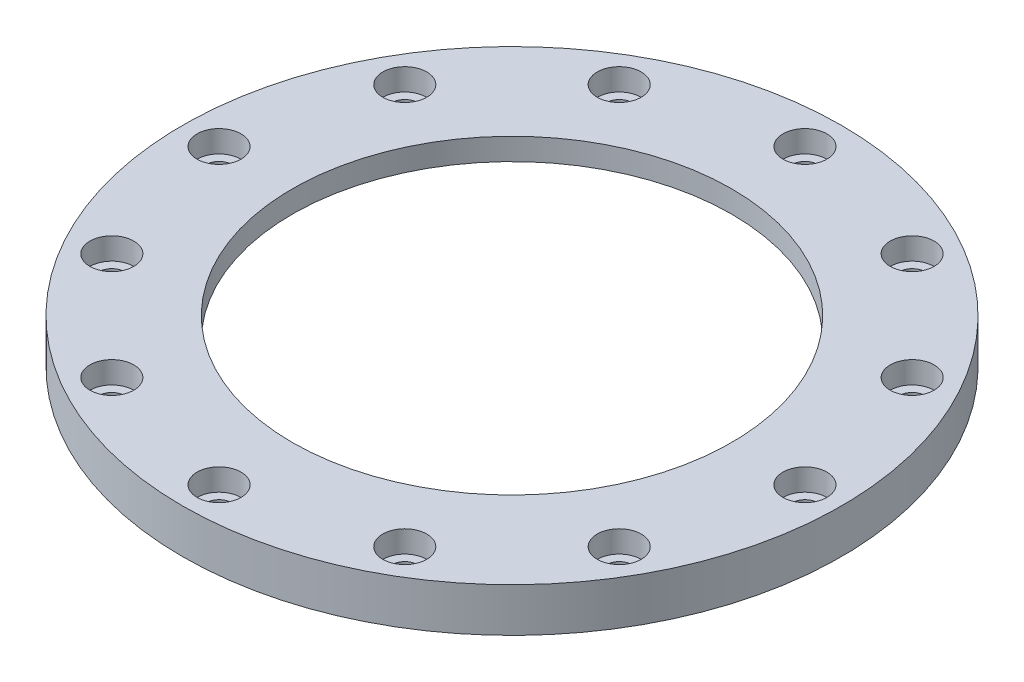
SolidWorks part; units mm, degrees
ref_plane "Front Plane" through (0, 0, 0) normal (0, 0, 1) x (1, 0, 0)
ref_plane "Top Plane" through (0, 0, 0) normal (0, 1, 0) x (1, 0, 0)
ref_plane "Right Plane" through (0, 0, 0) normal (1, 0, 0) x (0, 0, -1)
sketch "Sketch1" plane through (0, 0, 0) normal (0, 1, 0) x (1, 0, 0)
  line L0 (0, 0) -> (0, 52.0165) construction
  circle A0 centre (0, 0) radius 45
  circle A1 centre (0, 0) radius 30
  circle A2 centre (0, 0) radius 40 construction
  circle A3 centre (0, 40) radius 1.75
  circle A4 centre (0, 0) radius 36 construction
  circle A5 centre (20, 34.641) radius 1.75
  circle A6 centre (34.641, 20) radius 1.75
  circle A7 centre (40, 0) radius 1.75
  circle A8 centre (34.641, -20) radius 1.75
  circle A9 centre (20, -34.641) radius 1.75
  circle A10 centre (0, -40) radius 1.75
  circle A11 centre (-20, -34.641) radius 1.75
  circle A12 centre (-34.641, -20) radius 1.75
  circle A13 centre (-40, 0) radius 1.75
  circle A14 centre (-34.641, 20) radius 1.75
  circle A15 centre (-20, 34.641) radius 1.75
  point P21 (0, 0)
  point P34 (0, 0)
  point P48 (0, 0)
  point P72 (0, 0)
  dimension "D1" = 90
  dimension "D2" = 60
  dimension "D4" = 3.5
  dimension "D5" = 72
  dimension "D6" = 12
  dimension "D3" = 80
extrude "Boss-Extrude1" add sketch "Sketch1" along normal blind 6
sketch "Sketch2" plane through (0, 0, 0) normal (0, -1, 0) x (1, 0, 0)
  circle A0 centre (0, 0) radius 36
  dimension "D1" = 72
extrude "Cut-Extrude1" cut sketch "Sketch2" against normal blind 3
sketch "Sketch3" plane through (0, 6, 0) normal (0, 1, 0) x (1, 0, 0)
  line L0 (0, 0) -> (49.8808, 0) construction
  circle A0 centre (40, 0) radius 3
  circle A1 centre (34.641, -20) radius 3
  circle A2 centre (20, -34.641) radius 3
  circle A3 centre (0, -40) radius 3
  circle A4 centre (-20, -34.641) radius 3
  circle A5 centre (-34.641, -20) radius 3
  circle A6 centre (-40, 0) radius 3
  circle A7 centre (-34.641, 20) radius 3
  circle A8 centre (-20, 34.641) radius 3
  circle A9 centre (0, 40) radius 3
  circle A10 centre (20, 34.641) radius 3
  circle A11 centre (34.641, 20) radius 3
  point P30 (0, 0)
  dimension "D1" = 6
  dimension "D2" = 12
extrude "Cut-Extrude2" cut sketch "Sketch3" against normal blind 3
